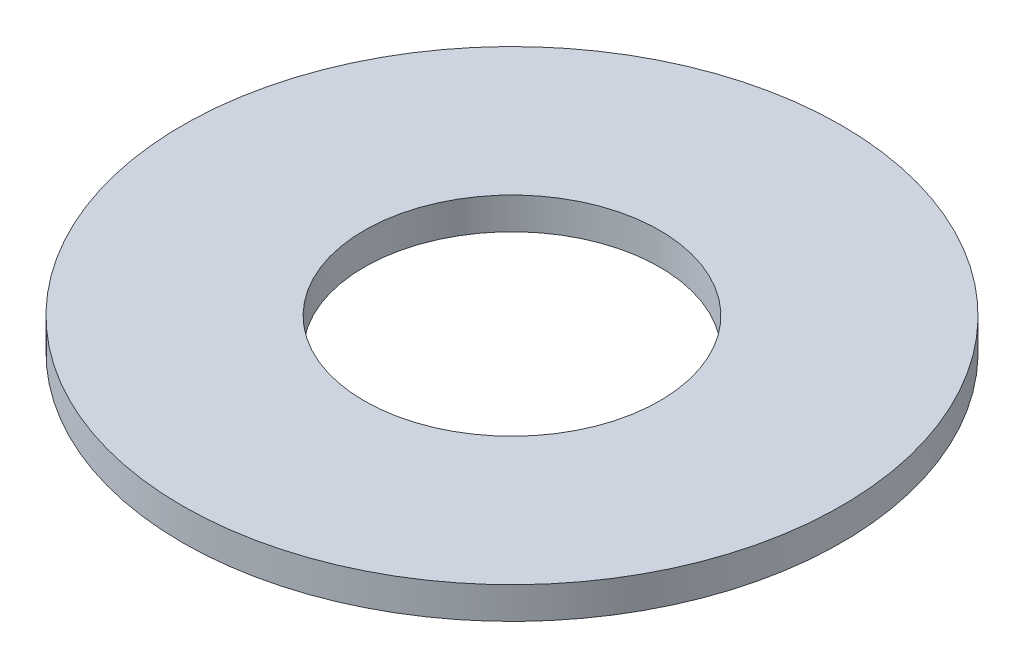
SolidWorks part; units mm, degrees
ref_plane "Front Plane" through (0, 0, 0) normal (0, 0, 1) x (1, 0, 0)
ref_plane "Top Plane" through (0, 0, 0) normal (0, 1, 0) x (1, 0, 0)
ref_plane "Right Plane" through (0, 0, 0) normal (1, 0, 0) x (0, 0, -1)
sketch "Sketch1" plane through (0, 0, 0) normal (0, 1, 0) x (1, 0, 0)
  circle A0 centre (0, 0) radius 72.5
  dimension "FLANGE_OD" = 145
extrude "Boss-Extrude1" add sketch "Sketch1" along normal blind 7
sketch "Sketch2" plane through (0, 0, 0) normal (0, 1, 0) x (1, 0, 0)
  circle A0 centre (0, 0) radius 32.5
  dimension "BORE_D" = 65
extrude "Cut-Extrude1" cut sketch "Sketch2" along normal through all
sketch "Sketch3" plane through (0, 7, 0) normal (0, 1, 0) x (1, 0, 0)
  circle A0 centre (0, 0) radius 25.0711 construction
  circle A1 centre (-25.0711, 0) radius 7.0928
  dimension "BOLT_D" = 14.1855
  dimension "BOLT_PCD" = 50.1421
extrude "Cut-Extrude2" cut sketch "Sketch3" against normal blind 6.4493 rebuild error yes
pattern_circular "CirPattern1" count 3 over 360 rebuild error yes
